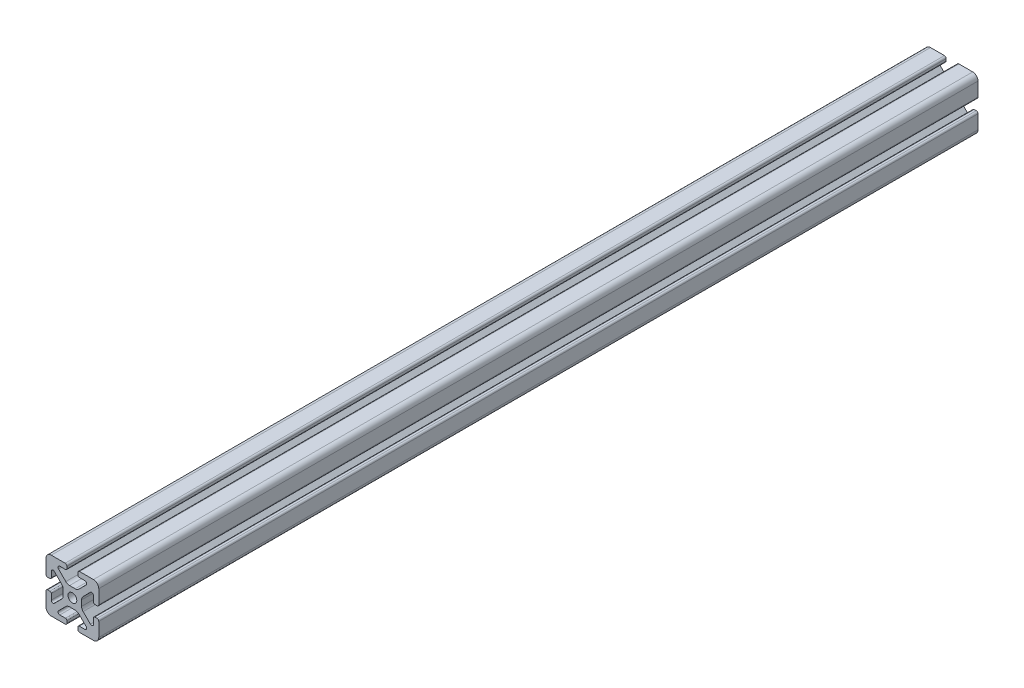
SolidWorks part; units mm, degrees
material "3003 Alloy"
ref_plane "Front Plane" through (0, 0, 0) normal (0, 0, 1) x (1, 0, 0)
ref_plane "Top Plane" through (0, 0, 0) normal (0, 1, 0) x (1, 0, 0)
ref_plane "Right Plane" through (0, 0, 0) normal (1, 0, 0) x (0, 0, -1)
sketch "Sketch1" plane through (0, 0, 0) normal (0, 0, 1) x (1, 0, 0)
  point P0 (5.1249, 1.9668)
  line B0 (1.6032, 5.25) -> (-1.6032, 5.25)
  arc B1 (-12, 15) -> (-15, 12) centre (-12, 12) ccw
  line B2 (-7.1276, 12) -> (-3.9, 12)
  line B3 (7.8506, 10.2547) -> (3.7245, 6.1287)
  line B4 (-10.2547, 7.8506) -> (-6.1287, 3.7245)
  line B5 (3.1, -12.8) -> (3.1, -14)
  arc B6 (3.9, -12) -> (3.1, -12.8) centre (3.9, -12.8) ccw
  line B7 (7.1276, -12) -> (3.9, -12)
  arc B8 (7.1276, -12) -> (7.8506, -10.2547) centre (7.1276, -10.9776) ccw
  line B9 (3.7245, -6.1287) -> (7.8506, -10.2547)
  arc B10 (3.7245, -6.1287) -> (1.6032, -5.25) centre (1.6032, -8.25) ccw
  line B11 (-1.6032, -5.25) -> (1.6032, -5.25)
  arc B12 (-1.6032, -5.25) -> (-3.7245, -6.1287) centre (-1.6032, -8.25) ccw
  line B13 (-7.8506, -10.2547) -> (-3.7245, -6.1287)
  arc B14 (-7.8506, -10.2547) -> (-7.1276, -12) centre (-7.1276, -10.9776) ccw
  line B15 (-3.9, -12) -> (-7.1276, -12)
  arc B16 (-3.1, -12.8) -> (-3.9, -12) centre (-3.9, -12.8) ccw
  line B17 (-3.1, -14) -> (-3.1, -12.8)
  arc B18 (-4.1, -15) -> (-3.1, -14) centre (-4.1, -14) ccw
  line B19 (-12, -15) -> (-4.1, -15)
  arc B20 (-15, -12) -> (-12, -15) centre (-12, -12) ccw
  line B21 (-15, -4.1) -> (-15, -12)
  arc B22 (-14, -3.1) -> (-15, -4.1) centre (-14, -4.1) ccw
  line B23 (-12.8, -3.1) -> (-14, -3.1)
  arc B24 (-12, -3.9) -> (-12.8, -3.1) centre (-12.8, -3.9) ccw
  line B25 (-12, -7.1276) -> (-12, -3.9)
  arc B26 (-12, -7.1276) -> (-10.2547, -7.8506) centre (-10.9776, -7.1276) ccw
  line B27 (-6.1287, -3.7245) -> (-10.2547, -7.8506)
  arc B28 (-6.1287, -3.7245) -> (-5.25, -1.6032) centre (-8.25, -1.6032) ccw
  line B29 (-5.25, 1.6032) -> (-5.25, -1.6032)
  arc B30 (-5.25, 1.6032) -> (-6.1287, 3.7245) centre (-8.25, 1.6032) ccw
  arc B31 (-10.2547, 7.8506) -> (-12, 7.1276) centre (-10.9776, 7.1276) ccw
  line B32 (-12, 3.9) -> (-12, 7.1276)
  arc B33 (-12.8, 3.1) -> (-12, 3.9) centre (-12.8, 3.9) ccw
  line B34 (-14, 3.1) -> (-12.8, 3.1)
  arc B35 (-15, 4.1) -> (-14, 3.1) centre (-14, 4.1) ccw
  line B36 (-15, 12) -> (-15, 4.1)
  line B37 (-4.1, 15) -> (-12, 15)
  arc B38 (-3.1, 14) -> (-4.1, 15) centre (-4.1, 14) ccw
  line B39 (-3.1, 12.8) -> (-3.1, 14)
  arc B40 (-3.9, 12) -> (-3.1, 12.8) centre (-3.9, 12.8) ccw
  arc B41 (-7.1276, 12) -> (-7.8506, 10.2547) centre (-7.1276, 10.9776) ccw
  line B42 (-3.7245, 6.1287) -> (-7.8506, 10.2547)
  arc B43 (-3.7245, 6.1287) -> (-1.6032, 5.25) centre (-1.6032, 8.25) ccw
  arc B44 (1.6032, 5.25) -> (3.7245, 6.1287) centre (1.6032, 8.25) ccw
  arc B45 (7.8506, 10.2547) -> (7.1276, 12) centre (7.1276, 10.9776) ccw
  line B46 (3.9, 12) -> (7.1276, 12)
  arc B47 (3.1, 12.8) -> (3.9, 12) centre (3.9, 12.8) ccw
  line B48 (3.1, 14) -> (3.1, 12.8)
  arc B49 (4.1, 15) -> (3.1, 14) centre (4.1, 14) ccw
  line B50 (12, 15) -> (4.1, 15)
  arc B51 (15, 12) -> (12, 15) centre (12, 12) ccw
  line B52 (15, 4.1) -> (15, 12)
  arc B53 (14, 3.1) -> (15, 4.1) centre (14, 4.1) ccw
  line B54 (12.8, 3.1) -> (14, 3.1)
  arc B55 (12, 3.9) -> (12.8, 3.1) centre (12.8, 3.9) ccw
  line B56 (12, 7.1276) -> (12, 3.9)
  arc B57 (12, 7.1276) -> (10.2547, 7.8506) centre (10.9776, 7.1276) ccw
  line B58 (6.1287, 3.7245) -> (10.2547, 7.8506)
  arc B59 (6.1287, 3.7245) -> (5.25, 1.6032) centre (8.25, 1.6032) ccw
  line B60 (5.25, -1.6032) -> (5.25, 1.6032)
  arc B61 (5.25, -1.6032) -> (6.1287, -3.7245) centre (8.25, -1.6032) ccw
  line B62 (10.2547, -7.8506) -> (6.1287, -3.7245)
  arc B63 (10.2547, -7.8506) -> (12, -7.1276) centre (10.9776, -7.1276) ccw
  line B64 (12, -3.9) -> (12, -7.1276)
  arc B65 (12.8, -3.1) -> (12, -3.9) centre (12.8, -3.9) ccw
  line B66 (14, -3.1) -> (12.8, -3.1)
  arc B67 (15, -4.1) -> (14, -3.1) centre (14, -4.1) ccw
  line B68 (15, -12) -> (15, -4.1)
  arc B69 (12, -15) -> (15, -12) centre (12, -12) ccw
  line B70 (4.1, -15) -> (12, -15)
  arc B71 (3.1, -14) -> (4.1, -15) centre (4.1, -14) ccw
  circle B72 centre (0, 0) radius 2.5
sketch_block_instance "IR 30X30 IR41901-2"
sketch_block "IR 30X30 IR41901"
extrude "Boss-Extrude1" add sketch "Sketch1" along normal blind 500
